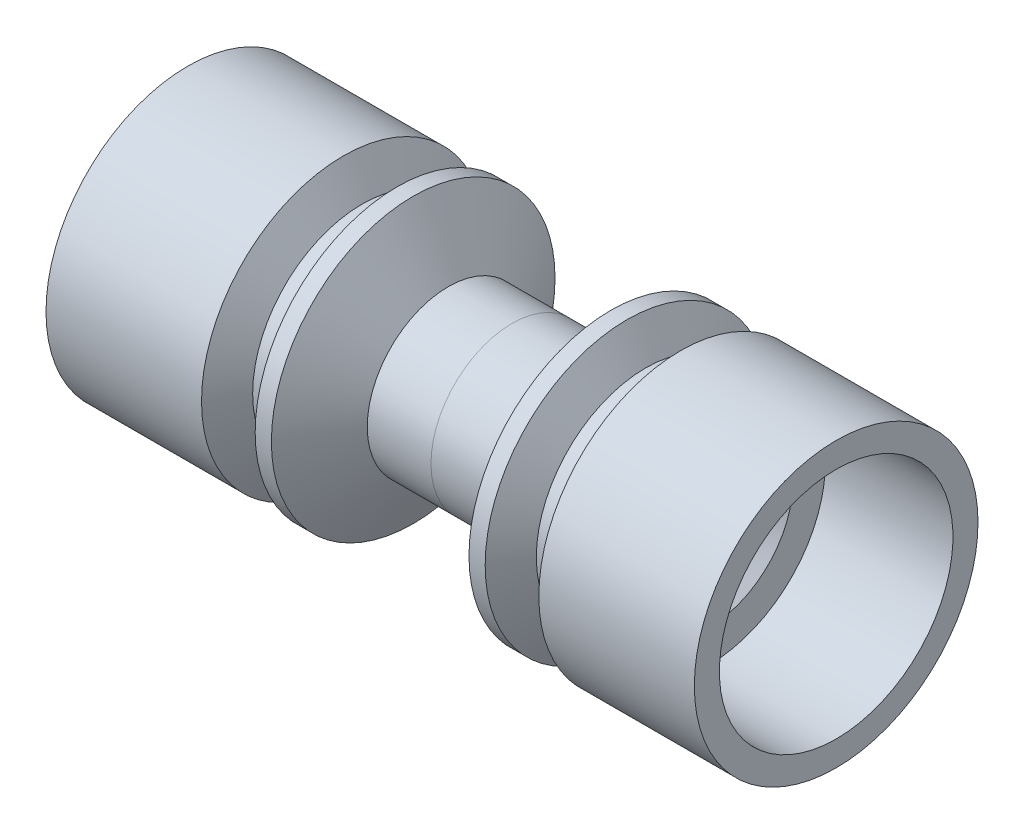
SolidWorks part; units mm, degrees
ref_plane "Front Plane" through (0, 0, 0) normal (0, 0, 1) x (1, 0, 0)
ref_plane "Top Plane" through (0, 0, 0) normal (0, 1, 0) x (1, 0, 0)
ref_plane "Right Plane" through (0, 0, 0) normal (1, 0, 0) x (0, 0, -1)
sketch "Sketch2" plane through (0, 0, 0) normal (0, 0, 1) x (1, 0, 0)
  line L0 (0, 0) -> (0, 28.4375) construction
  line L1 (-12.7, 4.575) -> (-7.7, 4.575) construction
  line L2 (-12.7, 4.575) -> (-12.7, -4.575) construction
  line L3 (-12.7, -4.575) -> (-7.7, -4.575) construction
  line L4 (-7.7, 4.575) -> (-7.7, -4.575) construction
  line L5 (-12.7, 4.575) -> (-7.7, -4.575) construction
  line L6 (-12.7, -4.575) -> (-7.7, 4.575) construction
  line L7 (7.7, 4.5) -> (55.8832, 4.5) construction
  line L8 (7.7, 4.5) -> (7.7, -4.5) construction
  line L9 (7.7, -4.5) -> (55.8832, -4.5) construction
  line L10 (55.8832, 4.5) -> (55.8832, -4.5) construction
  line L11 (7.7, 4.5) -> (55.8832, -4.5) construction
  line L12 (7.7, -4.5) -> (55.8832, 4.5) construction
  line L13 (-12.7, 0) -> (55.8832, 0) construction
  line L14 (-12.7, 5.5562) -> (-6.607, 5.5562)
  line L21 (-2.4957, 3.175) -> (0, 3.175)
  line L22 (-12.7, 5.5562) -> (-12.7, 4.575)
  line L23 (-12.7, 4.575) -> (-7.7, 4.575)
  line L24 (-7.7, 4.575) -> (-7.7, 0)
  line L25 (-7.7, 0) -> (0, 0)
  line L26 (0, 0) -> (0, 3.175)
  line L27 (-33.5594, -5.5562) -> (-33.5594, 5.5562) construction
  line L28 (-6.607, 5.5562) -> (-5.8737, 4.2863)
  line L29 (-5.8737, 4.2863) -> (-5.2387, 4.2863)
  line L30 (-12.7, 5.5562) -> (12.7, 5.5562) construction
  line L31 (0, 1.6) -> (-12.5, 1.6)
  line L32 (-12.5, 1.6) -> (-14.1, 0)
  line L33 (-12.5, 1.6) -> (-12.5, -1.6) construction
  line L34 (-12.5, 1.6) -> (12.5, 1.6) construction
  line L35 (-7.7, 1.7145) -> (-2.875, 1.7145)
  line L36 (-2.875, 1.7145) -> (-2.875, 0)
  line L37 (-7.7, 3.305) -> (-7.192, 2.797)
  line L38 (-2.875, 1.7145) -> (-15.875, 1.7145) construction
  line L39 (-2.875, 1.7145) -> (-2.875, -1.7145) construction
  line L40 (-2.875, -1.7145) -> (-15.875, -1.7145) construction
  line L41 (-15.875, 1.7145) -> (-15.875, -1.7145) construction
  line L42 (-7.192, 2.797) -> (-7.192, 0)
  line L46 (-5.2387, 4.2863) -> (-4.5055, 5.5563)
  line L47 (-4.5055, 5.5563) -> (-3.8705, 5.5563)
  line L48 (-3.8705, 5.5563) -> (-2.4957, 3.175)
  line L49 (-5.5562, 4.2863) -> (-5.5562, 6.3987) construction
  line L50 (-5.5562, 6.3987) -> (5.5562, 6.3987) construction
  point P0 (-10.2, 0)
  point P5 (31.7916, 0)
  point P27 (-33.5594, 0)
  point P29 (-12.5, 0)
  point P33 (0, 6.3987)
  point P36 (0, 1.6)
  point P48 (-2.875, 0)
  point P51 (0, 5.5562)
  dimension "D3" = 3.175
  dimension "D4" = 11.1125
  dimension "D5" = 9.15
  dimension "D6" = 60
  dimension "D7" = 0.635
  dimension "D8" = 60
  dimension "D9" = 11.1125
  dimension "D10" = 1.27
  dimension "D11" = 25.4
  dimension "D12" = 0.635
  dimension "D13" = 45
  dimension "D14" = 25
  dimension "D15" = 3.2
  dimension "D16" = 3.429
  dimension "D17" = 3.175
  dimension "D18" = 1.27
  dimension "D19" = 0.508
  dimension "D20" = 45
  dimension "D21" = 13
  dimension "D22" = 5
revolve "Revolve1" add sketch "Sketch2" angle 360 about L13 region at (-5.5371, 3.5788, 0)
mirror "Mirror1" about plane through (0, 0, 0) normal (1, 0, 0) of bodies 101
chamfer "Chamfer1" distance 0.508 angle 45 1 edges at (-12.7, -4.575, 0)
